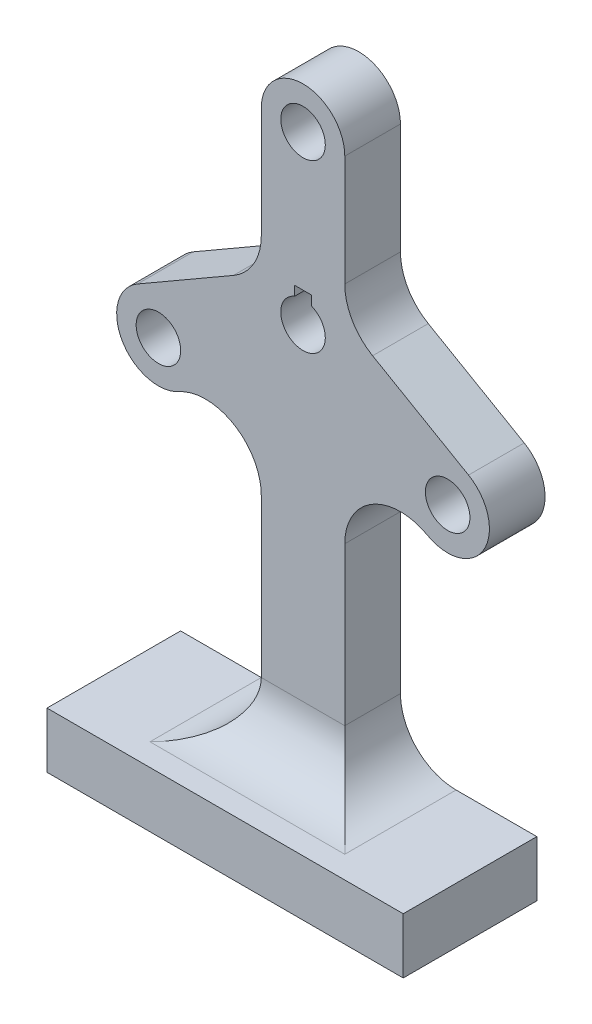
SolidWorks part; units mm, degrees
ref_plane "Front Plane" through (0, 0, 0) normal (0, 0, 1) x (1, 0, 0)
ref_plane "Top Plane" through (0, 0, 0) normal (0, 1, 0) x (1, 0, 0)
ref_plane "Right Plane" through (0, 0, 0) normal (1, 0, 0) x (0, 0, -1)
sketch "Sketch1" plane through (0, 0, 0) normal (0, 0, 1) x (1, 0, 0)
  line L1 (-7.5, 0) -> (7.5, 0)
  line L2 (-7.5, 0) -> (-7.5, 37.5)
  line L3 (-7.5, 37.5) -> (7.5, 37.5)
  line L4 (7.5, 0) -> (7.5, 37.5)
  circle A1 centre (0, 30) radius 7.5 construction
  point P6 (0, 0)
extrude "Boss-Extrude1" add sketch "Sketch1" along normal blind 10
ref_axis "Axis1" through (0, 0, -1.27) along (0, 0, 1)
pattern_circular "CirPattern1" count 3 over 360 about axis through (0, 0, -1.27) along (0, 0, 1) of "Boss-Extrude1"
sketch "Sketch2" plane through (0, 0, 10) normal (0, 0, 1) x (1, 0, 0)
  line L0 (0, 0) -> (-25.9808, -15) construction
  line L2 (-7.5, 4.3301) -> (-36.226, -12.2548) construction
  line L3 (-1.5, 5.4) -> (1.5, 5.4)
  line L4 (-1.5, 5.4) -> (-1.5, 0)
  line L5 (-1.5, 0) -> (1.5, 0)
  line L6 (1.5, 5.4) -> (1.5, 0)
  line L11 (-7.5, 37.5) -> (-7.5, 4.3301)
  line L12 (-7.5, 4.3301) -> (-36.226, -12.2548)
  line L13 (-36.226, -12.2548) -> (-28.726, -25.2452)
  line L14 (-28.726, -25.2452) -> (0, -8.6603)
  line L15 (0, -8.6603) -> (28.726, -25.2452)
  line L16 (28.726, -25.2452) -> (36.226, -12.2548)
  line L17 (36.226, -12.2548) -> (7.5, 4.3301)
  line L18 (7.5, 4.3301) -> (7.5, 37.5)
  line L19 (7.5, 37.5) -> (-7.5, 37.5)
  line L20 (-7.5, 37.5) -> (-7.5, 4.3301)
  line L21 (-7.5, 4.3301) -> (-36.226, -12.2548)
  line L22 (-36.226, -12.2548) -> (-28.726, -25.2452)
  line L23 (-28.726, -25.2452) -> (0, -8.6603)
  line L24 (0, -8.6603) -> (28.726, -25.2452)
  line L25 (28.726, -25.2452) -> (36.226, -12.2548)
  line L26 (36.226, -12.2548) -> (7.5, 4.3301)
  line L27 (7.5, 4.3301) -> (7.5, 37.5)
  line L28 (7.5, 37.5) -> (-7.5, 37.5)
  circle A0 centre (0, 0) radius 4
  circle A1 centre (-25.9808, -15) radius 4
  circle A2 centre (0, 30) radius 4
  circle A3 centre (25.9808, -15) radius 4
  circle A4 centre (0, 0) radius 4 construction
  dimension "D1" = 0
  dimension "D3" = 3
  dimension "D2" = 30
  dimension "D4" = 5.4
  dimension "D5" = 3
extrude "Cut-Extrude1" cut sketch "Sketch2" against normal through all contours L5 L0 A0 L6 | L0 L5 L4 A0 | L6 A0 L4 L5 | A0 L6 L3 L4 | A3 | A1 | A2 region at (1.0003, -1.0817, 10) region at (-2.5381, 0.6457, 10) region at (0, 1.953, 10) region at (-22.2263, -13.994, 10) region at (0, 4.6496, 10) region at (0, 30, 10) region at (25.9808, -15, 10)
sketch "Sketch3" plane through (0, 0, 0) normal (0, 0, -1) x (-1, 0, 0)
  line L1 (-7.5, -78.6182) -> (7.5, -78.6182)
  line L2 (-7.5, -78.6182) -> (-7.5, -5.7715)
  line L3 (-7.5, -5.7715) -> (7.5, -5.7715)
  line L4 (7.5, -78.6182) -> (7.5, -5.7715)
  point P4 (7.5, -78.6182)
  point P5 (0, -5.7715)
  dimension "D1" = 15
extrude "Boss-Extrude2" add sketch "Sketch3" against normal up to surface (10 mm away) up to face at (4, 30, 10)
sketch "Sketch4" plane through (0, 0, 10) normal (0, 0, 1) x (1, 0, 0)
  line L1 (-32, -78.6182) -> (32, -78.6182)
  line L2 (-32, -78.6182) -> (-32, -68.6182)
  line L3 (-32, -68.6182) -> (32, -68.6182)
  line L4 (32, -78.6182) -> (32, -68.6182)
  line L6 (-7.5, -78.6182) -> (7.5, -78.6182) construction
  point P8 (0, -78.6182)
  dimension "D1" = 10
  dimension "D2" = 64
extrude "Boss-Extrude3" add sketch "Sketch4" along normal blind 24 from surface starting at face at (0, -14.5464, 0)
fillet "Fillet2" 2 edges at (-7.5, 37.5, 5) (7.5, 37.5, 5) type full round first side face at (-7.5, 20.9151, 5) second side face at (7.5, 20.9151, 5) middle face at (0, 37.5, 5)
fillet "Fillet3" 2 edges at (36.226, -12.2548, 5) (28.726, -25.2452, 5) type full round first side face at (21.863, -3.9623, 5) second side face at (18.113, -19.1178, 5) middle face at (32.476, -18.75, 5)
fillet "Fillet4" 2 edges at (-28.726, -25.2452, 5) (-36.226, -12.2548, 5) type full round first side face at (-18.113, -19.1178, 5) second side face at (-21.863, -3.9623, 5) middle face at (-32.476, -18.75, 5)
fillet "Fillet5" radius 10 4 edges at (-7.5, 4.3301, 5) (7.5, 4.3301, 5) (-7.5, -12.9904, 5) (7.5, -12.9904, 5)
fillet "Fillet6" radius 10 3 edges at (7.5, -68.6182, 5) (0, -68.6182, 10) (-7.5, -68.6182, 5)
sketch "Sketch5" plane through (0, -78.6182, 0) normal (0, -1, 0) x (1, 0, 0)
  line L15 (-30.4, 22.4) -> (-30.4, 1.6)
  line L16 (-30.4, 1.6) -> (30.4, 1.6)
  line L17 (30.4, 1.6) -> (30.4, 22.4)
  line L18 (30.4, 22.4) -> (-30.4, 22.4)
  line L19 (-30.4, 22.4) -> (-30.4, 1.6)
  line L20 (-30.4, 1.6) -> (30.4, 1.6)
  line L21 (30.4, 1.6) -> (30.4, 22.4)
  line L22 (30.4, 22.4) -> (-30.4, 22.4)
  dimension "D1" = 1.6
extrude "Cut-Extrude2" cut sketch "Sketch5" against normal blind 8 contours L21 L22 L19 L20
sketch "Sketch6" plane through (0, -70.6182, 0) normal (0, -1, 0) x (1, 0, 0)
  line L0 (30.4, 12) -> (-30.4, 12) construction
  line L1 (23.6, 4.7687) -> (23.6, 1.6)
  line L2 (-30.4, 1.6) -> (30.4, 1.6) construction
  line L7 (30.4, 1.6) -> (30.4, 22.4) construction
  line L8 (-30.4, 22.4) -> (-30.4, 1.6) construction
  line L9 (32, 24) -> (32, 0) construction
  line L10 (32, 0) -> (-32, 0) construction
  line L11 (23.6, 1.6) -> (24.4, 1.6)
  line L12 (-30.4, 1.6) -> (30.4, 1.6) construction
  line L13 (24.4, 1.6) -> (24.4, 4.7687)
  line L14 (22.8512, 5.8928) -> (21.8928, 6.8512)
  line L15 (25.1488, 5.8928) -> (26.1072, 6.8512)
  line L16 (21.8928, 9.1488) -> (22.8512, 10.1072)
  line L17 (26.1072, 9.1488) -> (25.1488, 10.1072)
  line L18 (20.744, 8) -> (21.8928, 9.1488) construction
  line L19 (21.8928, 6.8512) -> (20.744, 8) construction
  line L20 (24, 4.744) -> (22.8512, 5.8928) construction
  line L21 (24, 4.744) -> (25.1488, 5.8928) construction
  line L22 (26.1072, 6.8512) -> (27.256, 8) construction
  line L23 (27.256, 8) -> (26.1072, 9.1488) construction
  line L24 (25.1488, 10.1072) -> (24, 11.256) construction
  line L25 (22.8512, 10.1072) -> (24, 11.256) construction
  line L26 (23.6, 11.2313) -> (23.6, 12.7687)
  line L27 (24.4, 11.2313) -> (24.4, 12.7687)
  line L28 (22.8512, 13.8928) -> (24, 12.744) construction
  line L29 (25.1488, 13.8928) -> (24, 12.744) construction
  line L30 (27.256, 16) -> (26.1072, 14.8512) construction
  line L31 (26.1072, 17.1488) -> (27.256, 16) construction
  line L32 (24, 19.256) -> (25.1488, 18.1072) construction
  line L33 (24, 19.256) -> (22.8512, 18.1072) construction
  line L34 (21.8928, 17.1488) -> (20.744, 16) construction
  line L35 (20.744, 16) -> (21.8928, 14.8512) construction
  line L36 (26.1072, 14.8512) -> (25.1488, 13.8928)
  line L37 (21.8928, 14.8512) -> (22.8512, 13.8928)
  line L38 (25.1488, 18.1072) -> (26.1072, 17.1488)
  line L39 (22.8512, 18.1072) -> (21.8928, 17.1488)
  line L40 (24.4, 22.4) -> (24.4, 19.2313)
  line L41 (23.6, 22.4) -> (24.4, 22.4)
  line L42 (23.6, 19.2313) -> (23.6, 22.4)
  line L43 (19.6, 1.6) -> (19.6, 2)
  line L44 (27.6, 1.6) -> (28.4, 1.6)
  line L45 (27.6, 1.6) -> (27.6, 2)
  line L46 (27.6, 2) -> (28.4, 2)
  line L47 (28.4, 1.6) -> (28.4, 2)
  line L48 (19.6, 1.6) -> (20.4, 1.6)
  line L49 (30.4, 4.4) -> (30, 4.4)
  line L50 (30.4, 4.4) -> (30.4, 3.6)
  line L51 (30.4, 3.6) -> (30, 3.6)
  line L52 (30, 4.4) -> (30, 3.6)
  line L53 (20.4, 1.6) -> (20.4, 2)
  line L54 (19.6, 2) -> (20.4, 2)
  line L55 (11.6, 1.6) -> (11.6, 2)
  line L56 (11.6, 1.6) -> (12.4, 1.6)
  line L57 (12.4, 1.6) -> (12.4, 2)
  line L58 (11.6, 2) -> (12.4, 2)
  line L59 (3.6, 1.6) -> (3.6, 2)
  line L60 (3.6, 1.6) -> (4.4, 1.6)
  line L61 (4.4, 1.6) -> (4.4, 2)
  line L62 (3.6, 2) -> (4.4, 2)
  line L63 (-4.4, 1.6) -> (-4.4, 2)
  line L64 (-4.4, 1.6) -> (-3.6, 1.6)
  line L65 (-3.6, 1.6) -> (-3.6, 2)
  line L66 (-4.4, 2) -> (-3.6, 2)
  line L67 (-12.4, 1.6) -> (-12.4, 2)
  line L68 (-12.4, 1.6) -> (-11.6, 1.6)
  line L69 (-11.6, 1.6) -> (-11.6, 2)
  line L70 (-12.4, 2) -> (-11.6, 2)
  line L71 (-20.4, 1.6) -> (-20.4, 2)
  line L72 (-20.4, 1.6) -> (-19.6, 1.6)
  line L73 (-19.6, 1.6) -> (-19.6, 2)
  line L74 (-20.4, 2) -> (-19.6, 2)
  line L75 (-28.4, 1.6) -> (-28.4, 2)
  line L76 (-28.4, 1.6) -> (-27.6, 1.6)
  line L77 (-27.6, 1.6) -> (-27.6, 2)
  line L78 (-28.4, 2) -> (-27.6, 2)
  line L79 (30.4, 12.4) -> (30, 12.4)
  line L80 (30.4, 12.4) -> (30.4, 11.6)
  line L81 (30.4, 11.6) -> (30, 11.6)
  line L82 (30, 12.4) -> (30, 11.6)
  line L83 (30.4, 20.4) -> (30, 20.4)
  line L84 (30.4, 20.4) -> (30.4, 19.6)
  line L85 (30.4, 19.6) -> (30, 19.6)
  line L86 (30, 20.4) -> (30, 19.6)
  line L87 (0, 1.6) -> (0, 22.4) construction
  line L88 (30.4, 22.4) -> (-30.4, 22.4) construction
  line L89 (-30, 20.4) -> (-30, 19.6)
  line L90 (-30.4, 19.6) -> (-30, 19.6)
  line L91 (-30.4, 20.4) -> (-30.4, 19.6)
  line L92 (-30.4, 20.4) -> (-30, 20.4)
  line L93 (-30, 12.4) -> (-30, 11.6)
  line L94 (-30.4, 11.6) -> (-30, 11.6)
  line L95 (-30.4, 12.4) -> (-30.4, 11.6)
  line L96 (-30.4, 12.4) -> (-30, 12.4)
  line L97 (-30, 4.4) -> (-30, 3.6)
  line L98 (-30.4, 3.6) -> (-30, 3.6)
  line L99 (-30.4, 4.4) -> (-30.4, 3.6)
  line L100 (-30.4, 4.4) -> (-30, 4.4)
  line L101 (27.6, 22) -> (28.4, 22)
  line L102 (28.4, 22.4) -> (28.4, 22)
  line L103 (27.6, 22.4) -> (28.4, 22.4)
  line L104 (27.6, 22.4) -> (27.6, 22)
  line L105 (-28.4, 22) -> (-27.6, 22)
  line L106 (-27.6, 22.4) -> (-27.6, 22)
  line L107 (-28.4, 22.4) -> (-27.6, 22.4)
  line L108 (-28.4, 22.4) -> (-28.4, 22)
  line L109 (-20.4, 22) -> (-19.6, 22)
  line L110 (-19.6, 22.4) -> (-19.6, 22)
  line L111 (-20.4, 22.4) -> (-19.6, 22.4)
  line L112 (-20.4, 22.4) -> (-20.4, 22)
  line L113 (-12.4, 22) -> (-11.6, 22)
  line L114 (-11.6, 22.4) -> (-11.6, 22)
  line L115 (-12.4, 22.4) -> (-11.6, 22.4)
  line L116 (-12.4, 22.4) -> (-12.4, 22)
  line L117 (-4.4, 22) -> (-3.6, 22)
  line L118 (-3.6, 22.4) -> (-3.6, 22)
  line L119 (-4.4, 22.4) -> (-3.6, 22.4)
  line L120 (-4.4, 22.4) -> (-4.4, 22)
  line L121 (3.6, 22) -> (4.4, 22)
  line L122 (4.4, 22.4) -> (4.4, 22)
  line L123 (3.6, 22.4) -> (4.4, 22.4)
  line L124 (3.6, 22.4) -> (3.6, 22)
  line L125 (11.6, 22) -> (12.4, 22)
  line L126 (12.4, 22.4) -> (12.4, 22)
  line L127 (11.6, 22.4) -> (12.4, 22.4)
  line L128 (11.6, 22.4) -> (11.6, 22)
  line L129 (19.6, 22) -> (20.4, 22)
  line L130 (20.4, 22.4) -> (20.4, 22)
  line L131 (19.6, 22.4) -> (20.4, 22.4)
  line L132 (19.6, 22.4) -> (19.6, 22)
  arc A2 (21.8928, 9.1488) -> (21.8928, 6.8512) centre (24, 8) ccw
  arc A3 (24.4, 4.7687) -> (24.4, 11.2313) centre (24, 8) ccw
  arc A4 (23.6, 4.7687) -> (24.4, 4.7687) centre (24, 8) ccw construction
  arc A5 (22.8512, 10.1072) -> (21.8928, 9.1488) centre (24, 8) ccw construction
  arc A6 (21.8928, 6.8512) -> (22.8512, 5.8928) centre (24, 8) ccw construction
  arc A7 (22.8512, 5.8928) -> (25.1488, 5.8928) centre (24, 8) ccw
  arc A8 (25.1488, 5.8928) -> (26.1072, 6.8512) centre (24, 8) ccw construction
  arc A9 (26.1072, 6.8512) -> (26.1072, 9.1488) centre (24, 8) ccw
  arc A10 (26.1072, 9.1488) -> (25.1488, 10.1072) centre (24, 8) ccw construction
  arc A11 (25.1488, 10.1072) -> (22.8512, 10.1072) centre (24, 8) ccw
  arc A12 (26.1072, 14.8512) -> (25.1488, 13.8928) centre (24, 16) cw construction
  arc A13 (25.1488, 18.1072) -> (26.1072, 17.1488) centre (24, 16) cw construction
  arc A14 (21.8928, 17.1488) -> (22.8512, 18.1072) centre (24, 16) cw construction
  arc A15 (22.8512, 13.8928) -> (21.8928, 14.8512) centre (24, 16) cw construction
  arc A16 (23.6, 19.2313) -> (24.4, 19.2313) centre (24, 16) cw construction
  arc A17 (25.1488, 13.8928) -> (22.8512, 13.8928) centre (24, 16) cw
  arc A18 (26.1072, 17.1488) -> (26.1072, 14.8512) centre (24, 16) cw
  arc A19 (22.8512, 18.1072) -> (25.1488, 18.1072) centre (24, 16) cw
  arc A20 (24.4, 19.2313) -> (24.4, 12.7687) centre (24, 16) cw
  arc A21 (21.8928, 14.8512) -> (21.8928, 17.1488) centre (24, 16) cw
  arc A22 (24, 11.256) -> (23.6, 11.2313) centre (24, 8) ccw construction
  arc A23 (23.6, 11.2313) -> (23.6, 4.7687) centre (24, 8) ccw
  arc A24 (24.4, 11.2313) -> (24, 11.256) centre (24, 8) ccw construction
  arc A25 (24, 12.744) -> (23.6, 12.7687) centre (24, 16) cw construction
  arc A26 (23.6, 12.7687) -> (23.6, 19.2313) centre (24, 16) cw
  arc A27 (24.4, 12.7687) -> (24, 12.744) centre (24, 16) cw construction
  point P21 (24, 1.6)
  point P52 (24.4, 12)
  point P53 (23.6, 12)
  point P59 (30.4, 4)
  point P60 (28, 1.6)
  line M10 (30.4, 1.6) -> (30.4, 22.4)
  line M11 (30.4, 22.4) -> (-30.4, 22.4)
  line M12 (-30.4, 22.4) -> (-30.4, 1.6)
  line M13 (-30.4, 1.6) -> (30.4, 1.6)
  dimension "D1" = 4.8
  dimension "D2" = 6.512
  dimension "D3" = 8
  dimension "D4" = 8
  dimension "D5" = 0.8
  dimension "D6" = 0.4
  dimension "D7" = 0.8
  dimension "D8" = 2.4
  dimension "D9" = 2.4
  dimension "D10" = 8
  dimension "D11" = 3
extrude "Boss-Extrude4" add sketch "Sketch6" along normal up to surface (8 mm away) contours A26 L26 A23 L1 L13 A3 L27 A20 L40 L42 A11 L17 A9 L15 A7 L14 A2 L16 L37 A21 L39 A19 L38 A18 L36 A17 M13 M11 region at (24, -70.6182, 12) up to face at (0, -78.6182, 12)
pattern_linear "LPattern1" count 7 spacing 8 along (-1, 0, 0) of "Boss-Extrude4"
extrude "Boss-Extrude5" add sketch "Sketch6<3>" along normal blind 8 contours L54 L43 L53 M13 | L58 L55 L57 M13 | L62 L59 L61 M13 | L66 L63 L65 M13 | L70 L67 L69 M13 | L78 L75 L77 M13 | L100 L98 L97 M12 | L96 L94 L93 M12 | L92 L90 L89 M12 | L116 L113 L114 M11 | L124 L121 L122 M11 | L128 L125 L126 M11 | L132 L129 L130 M11 | L104 L101 L102 M11 | L79 L82 L81 M10 | L46 L47 L44 L45 | L52 L51 L50 L49 | L74 L73 L72 L71 | L106 L105 L108 L107 | L111 L110 L109 L112 | L119 L118 L117 L120 | L83 L86 L85 L84 region at (20, -70.6182, 1.8) region at (12, -70.6182, 1.8) region at (20, -70.6182, 22.2) region at (4, -70.6182, 1.8) region at (28, -70.6182, 22.2) region at (12, -70.6182, 22.2) region at (30.2, -70.6182, 12) region at (-4, -70.6182, 1.8) region at (4, -70.6182, 22.2) region at (-12, -70.6182, 1.8) region at (-12, -70.6182, 22.2) region at (-28, -70.6182, 1.8) region at (-30.2, -70.6182, 4) region at (-30.2, -70.6182, 12) region at (-30.2, -70.6182, 20)
sketch "Sketch6<3>" plane through (0, -70.6182, 0) normal (0, -1, 0) x (1, 0, 0) same geometry as "Sketch6"
